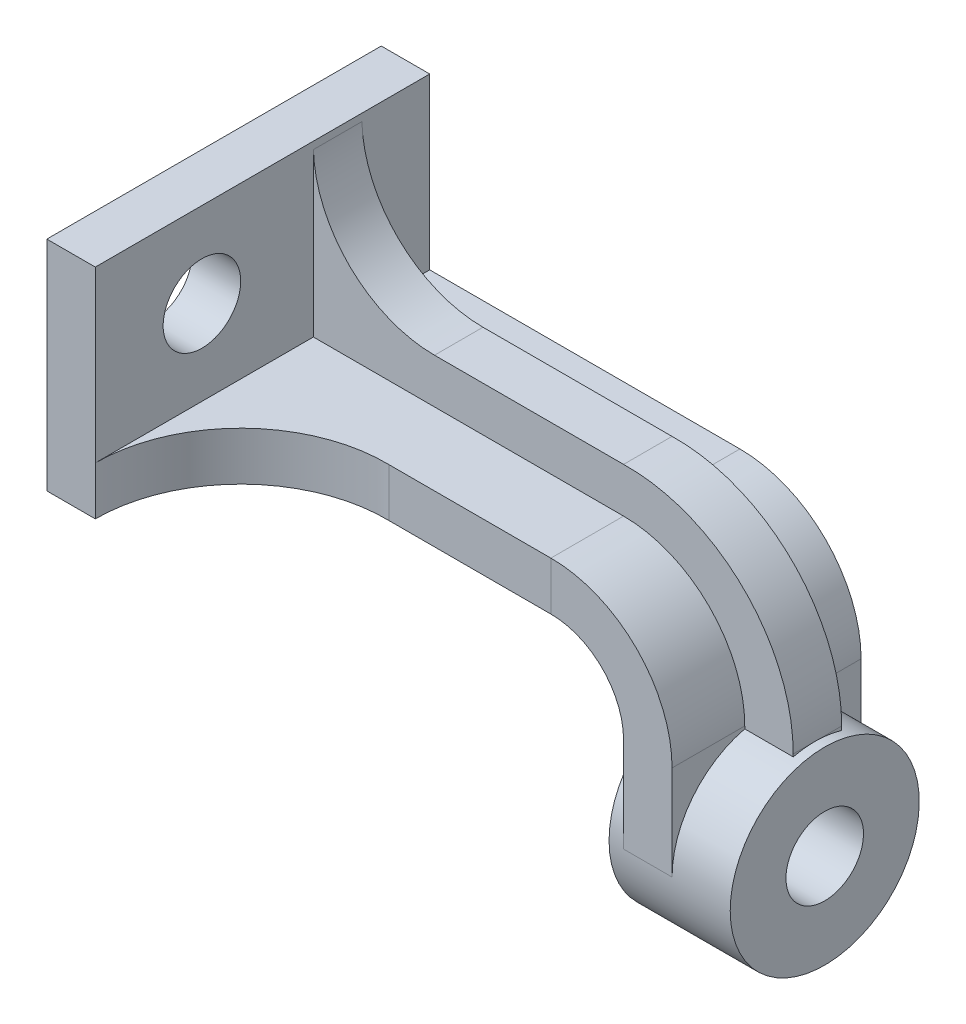
SolidWorks part; units mm, degrees
ref_plane "Front Plane" through (0, 0, 0) normal (0, 0, 1) x (1, 0, 0)
ref_plane "Top Plane" through (0, 0, 0) normal (0, 1, 0) x (1, 0, 0)
ref_plane "Right Plane" through (0, 0, 0) normal (1, 0, 0) x (0, 0, -1)
sketch "Sketch1" plane through (0, 0, 0) normal (1, 0, 0) x (0, 0, -1)
  line L0 (-25.6543, 0) -> (43.3457, 0)
  line L1 (43.3457, 0) -> (43.3457, 45)
  line L2 (43.3457, 45) -> (-25.6543, 45)
  line L3 (-25.6543, 45) -> (-25.6543, 0)
  dimension "D1" = 45
  dimension "D2" = 69
extrude "Boss-Extrude1" add sketch "Sketch1" against normal blind 10
sketch "Sketch2" plane through (0, 0, 25.6543) normal (0, 0, 1) x (1, 0, 0)
  line L0 (0, 10) -> (64, 10)
  line L1 (0, 45) -> (0, 0) construction
  line L2 (0, 10) -> (0, 0)
  line L3 (0, 0) -> (44.8544, 0)
  line L4 (89, -15) -> (89, -55.3678)
  line L5 (54.8544, 0) -> (54.8544, 0)
  line L6 (54.8544, 0) -> (54.8544, 0)
  line L7 (44.8544, 0) -> (64, 0)
  line L8 (79, -15) -> (79, -55.3678)
  line L9 (79, -55.3678) -> (89, -55.3678)
  line L11 (54.8544, 0) -> (64, 0) construction
  arc A0 (89, -15) -> (64, 10) centre (64, -15) ccw
  arc A2 (64, 0) -> (79, -15) centre (64, -15) cw
  arc A4 (79, -15) -> (64, 0) centre (64, -15) ccw construction
  line M9 (0, 0) -> (0, 45)
  dimension "D1" = 25
  dimension "D3" = 10
  dimension "D4" = 89
  dimension "D2" = 10
extrude "Boss-Extrude2" add sketch "Sketch2" against normal blind 69 contours L3 L8 L9 L4 A0 L0 M9 region at (32, 8.8957, 25.6543)
sketch "Sketch4" plane through (0, 10, 0) normal (0, 1, 0) x (1, 0, 0)
  line L0 (0, -25.6543) -> (64, -25.6543)
  line L1 (30.6436, 4.3387) -> (64, 4.3387)
  line L2 (64, 43.3457) -> (64, -25.6543) construction
  line L3 (0, -25.6543) -> (64, -25.6543)
  line L4 (64, -25.6543) -> (64, 4.3387)
  arc A0 (0, -25.6543) -> (30.6436, 4.3387) centre (30, -25.6543) cw
  line M2 (0, -25.6543) -> (64, -25.6543)
  line M3 (64, -25.6543) -> (64, 43.3457)
  dimension "D1" = 30
extrude "Cut-Extrude1" cut sketch "Sketch4" against normal blind 69 contours A0 L1 M2 M3 region at (34.8279, 10, 11.5847)
sketch "Sketch5" plane through (0, 0, 25.6543) normal (0, 0, 1) x (1, 0, 0)
  line L0 (79, -55.3678) -> (89, -55.3678)
  line L1 (89, -55.3678) -> (89, -15)
  line L2 (89, -15) -> (79, -15)
  line L3 (79, -15) -> (79, -55.3678)
  line L4 (64, 0) -> (64, 10)
  arc A0 (79, -15) -> (64, 0) centre (64, -15) ccw construction
  arc A1 (64, 10) -> (89, -15) centre (64, -15) cw
  arc A2 (64, 0) -> (79, -15) centre (64, -15) cw
  line M1 (64, 10) -> (64, 0)
  arc M2 (64, 0) -> (79, -15) centre (64, -15) cw
  line M3 (79, -15) -> (79, -55.3678)
  line M4 (79, -55.3678) -> (89, -55.3678)
  line M5 (89, -55.3678) -> (89, -15)
  arc M6 (89, -15) -> (64, 10) centre (64, -15) ccw
extrude "Cut-Extrude2" cut sketch "Sketch5" against normal blind 30 contours L2 M6 M1 M2 | L2 M5 M3 M4 region at (84, -35.1839, 25.6543) region at (76.9977, -2.0023, 25.6543)
sketch "Sketch6" plane through (89, 0, 0) normal (1, 0, 0) x (0, 0, -1)
  line L5 (43.3457, -15) -> (4.3457, -15) construction
  circle A1 centre (23.8457, -34.5) radius 19.5
extrude "Boss-Extrude3" add sketch "Sketch6" along normal blind 12
sketch "Sketch7" plane through (89, 0, 0) normal (1, 0, 0) x (0, 0, -1)
  line L0 (4.3457, -34.5) -> (4.3457, -55.3678)
  line L1 (4.3457, -55.3678) -> (43.3457, -55.3678)
  line L2 (43.3457, -55.3678) -> (43.3457, -34.5)
  arc A0 (4.3457, -34.5) -> (43.3457, -34.5) centre (23.8457, -34.5) ccw
extrude "Cut-Extrude3" cut sketch "Sketch7" against normal blind 12
sketch "Sketch8" plane through (79, 0, 0) normal (-1, 0, 0) x (0, 0, 1)
  circle A0 centre (-23.8457, -34.5) radius 19.5
extrude "Boss-Extrude4" add sketch "Sketch8" along normal blind 3
sketch "Sketch9" plane through (0, 0, 0) normal (1, 0, 0) x (0, 0, -1)
  line L0 (-25.6543, 45) -> (-25.6543, 10) construction
  circle A0 centre (-3.6543, 27.5) radius 8
  dimension "D1" = 22
extrude "Cut-Extrude4" cut sketch "Sketch9" against normal up to next
ref_plane "Plane1" through (0, 0, -24.3457) normal (0, 0, -1) x (-1, 0, 0)
sketch "Sketch13" plane through (0, 0, -24.3457) normal (0, 0, -1) x (-1, 0, 0)
  line L0 (0, 45) -> (0, 10)
  line L1 (0, 10) -> (-64, 10)
  line L2 (-89, -15) -> (-89, -34.5)
  line L3 (-89, -34.5) -> (-99, -34.5)
  line L4 (-99, -34.5) -> (-99, -15)
  line L5 (-89, -15) -> (-101, -15) construction
  line L6 (-24.9886, 19.2438) -> (-64, 19.2438)
  line L7 (-15.1655, 44.2438) -> (-15.1655, 45)
  line L9 (-99, -15) -> (-89, -15)
  arc A0 (-89, -15) -> (-64, 10) centre (-64, -15) cw
  arc A1 (-99, -15) -> (-64, 19.2438) centre (-64.7481, -15) cw
  arc A3 (-24.9886, 19.2438) -> (0, 45) centre (-24.9886, 44.2438) ccw
  dimension "D2" = 25
  dimension "D1" = 10
extrude "Boss-Extrude5" add sketch "Sketch13" along normal mid plane 10 contours A3 L6 A1 L9 A0 L1 L0 | L9 L4 L3 L2 region at (48.8812, 11.6401, -24.3457) region at (94, -24.75, -24.3457)
sketch "Sketch14" plane through (101, 0, 0) normal (1, 0, 0) x (0, 0, -1)
  circle A0 centre (23.8457, -34.5) radius 8
extrude "Cut-Extrude5" cut sketch "Sketch14" against normal up to next
